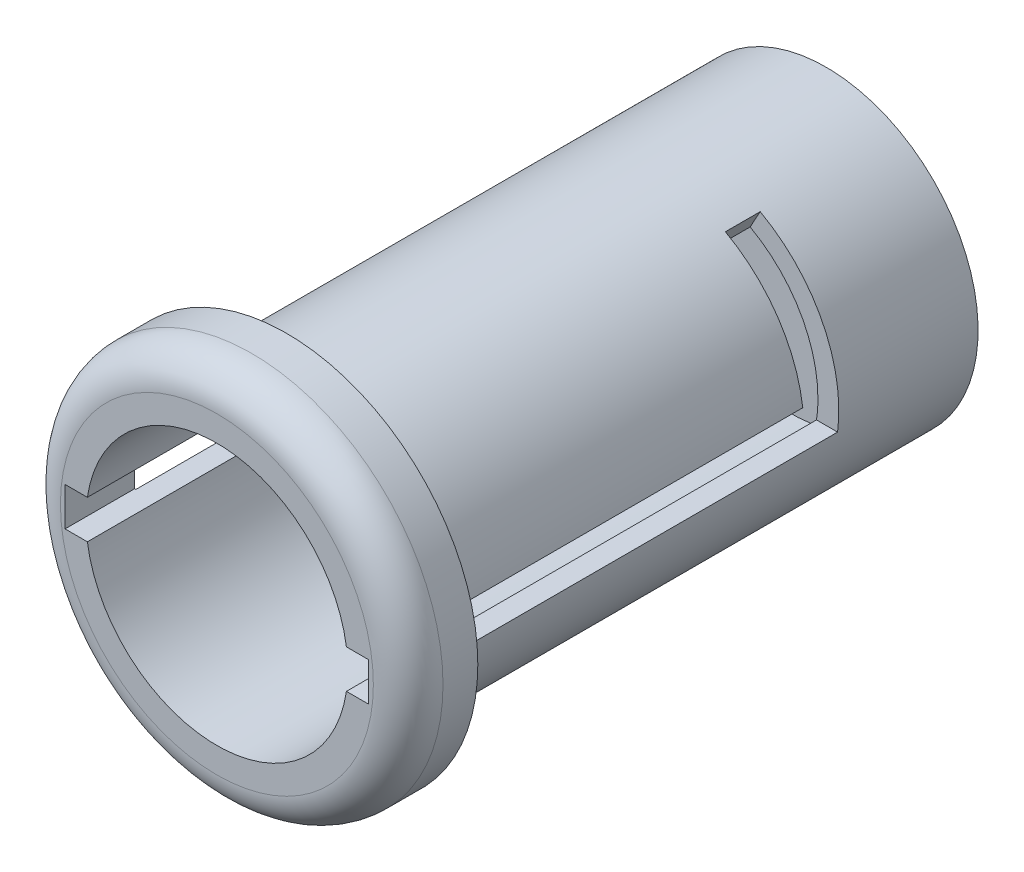
SolidWorks part; units mm, degrees
ref_plane "Front Plane" through (0, 0, 0) normal (0, 0, 1) x (1, 0, 0)
ref_plane "Top Plane" through (0, 0, 0) normal (0, 1, 0) x (1, 0, 0)
ref_plane "Right Plane" through (0, 0, 0) normal (1, 0, 0) x (0, 0, -1)
sketch "Sketch1" plane through (0, 0, 0) normal (0, 0, 1) x (1, 0, 0)
  circle A0 centre (-32.5, -25) radius 8.721
  arc A1 (-41.221, -25) -> (-23.779, -25) centre (-32.5, -25) ccw construction
  circle A2 centre (-32.5, -25) radius 7.521
  dimension "D1" = 1.2
extrude "Boss-Extrude1" add sketch "Sketch1" along normal blind 3 and the other way blind 30
sketch "Sketch2" plane through (0, 0, 3) normal (0, 0, 1) x (1, 0, 0)
  circle A0 centre (-32.5, -25) radius 10.987
  circle A1 centre (-32.5, -25) radius 7.521
  circle A2 centre (-32.5, -25) radius 7.521 construction
extrude "Boss-Extrude2" add sketch "Sketch2" against normal blind 4
fillet "Fillet1" radius 2 1 edges at (-21.513, -25, 3)
chamfer "Chamfer1" distance 2 angle 45 rebuild error yes
sketch "Sketch4" plane through (0, 0, 3) normal (0, 0, 1) x (1, 0, 0)
  line L1 (-23.779, -23.8942) -> (-41.221, -23.8942)
  line L2 (-23.779, -23.8942) -> (-23.779, -26.1058)
  line L3 (-23.779, -26.1058) -> (-41.221, -26.1058)
  line L4 (-41.221, -23.8942) -> (-41.221, -26.1058)
  line L5 (-23.779, -23.8942) -> (-41.221, -26.1058) construction
  line L6 (-23.779, -26.1058) -> (-41.221, -23.8942) construction
  circle A1 centre (-32.5, -25) radius 8.721 construction
  point P0 (-32.5, -25)
extrude "Cut-Extrude1" cut sketch "Sketch4" against normal through all
chamfer "Chamfer2" distance 1 angle 45 rebuild error yes
sketch "Sketch5" plane through (0, 0, 3) normal (0, 0, 1) x (1, 0, 0)
  line L0 (-28.2926, -17.3611) -> (-28.8715, -18.4122)
  line L1 (-23.8494, -26.1058) -> (-25.0608, -26.1058)
  arc A0 (-23.8494, -26.1058) -> (-28.2926, -17.3611) centre (-32.5, -25) ccw
  arc A1 (-23.8494, -23.8942) -> (-41.1506, -23.8942) centre (-32.5, -25) ccw construction
  arc A3 (-25.0608, -26.1058) -> (-28.8715, -18.4122) centre (-32.5, -25) ccw
  arc A4 (-25.0608, -23.8942) -> (-39.9392, -23.8942) centre (-32.5, -25) ccw construction
  arc A5 (-23.8494, -23.8942) -> (-41.1506, -23.8942) centre (-32.5, -25) ccw construction
extrude "Cut-Extrude2" cut sketch "Sketch5" against normal blind 2 from offset 25 offset against normal yes
pattern_circular "CirPattern1" count 2 over 360 about axis through (-32.5, -25, -30) along (0, 0, 1) of "Cut-Extrude2"
sketch "Sketch7" plane through (0, 0, -30) normal (0, 0, -1) x (-1, 0, 0)
  circle A0 centre (32.5, -25) radius 7.521
  circle A1 centre (32.5, -25) radius 8.721
  arc A2 (23.8494, -26.1058) -> (41.1506, -26.1058) centre (32.5, -25) ccw construction
  arc A3 (25.0608, -26.1058) -> (39.9392, -26.1058) centre (32.5, -25) ccw construction
extrude "Boss-Extrude5" add sketch "Sketch7" against normal up to vertex (6 mm away) up to point (-39.9392, -26.1058, -24)
sketch "Sketch6" plane through (0, 0, -30) normal (0, 0, -1) x (-1, 0, 0)
  circle A0 centre (32.5, -25) radius 8.721
  circle A2 centre (32.5, -25) radius 8.721 construction
extrude "Boss-Extrude4" add sketch "Sketch6" along normal blind 2
scale "Scale1" bodies to scale 111 scale about centroid uniform scaling yes scale factor 1.15
ref_plane "Plane1" [suppressed] through (-32.5, 0, 0) normal (1, 0, 0) x (0, 0, -1)
